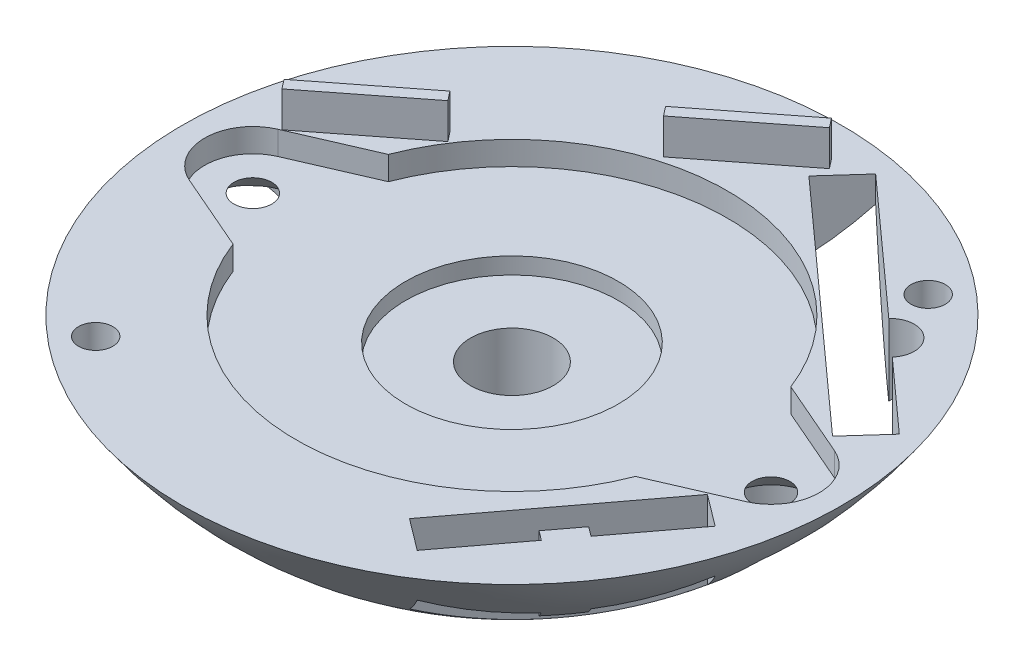
SolidWorks part; units mm, degrees
other "Markup1"
sketch "Sketch19" plane through (27.886, -16.1, -27.886) normal (0.7153, 0.5102, -0.4776) x (-0.4514, -0.1845, -0.8731)
ref_plane "Front Plane" through (0, 0, 0) normal (0, 0, 1) x (1, 0, 0)
ref_plane "Top Plane" through (0, 0, 0) normal (0, 1, 0) x (1, 0, 0)
ref_plane "Right Plane" through (0, 0, 0) normal (1, 0, 0) x (0, 0, -1)
sketch "Sketch1" plane through (0, 0, 0) normal (0, 0, 1) x (1, 0, 0)
  line L0 (0, -33.8) -> (0, 0)
  line L1 (33.8, 0) -> (0, 0)
  arc A0 (0, -33.8) -> (33.8, 0) centre (0, 0) ccw
  dimension "D1" = 33.8
revolve "Revolve1" add sketch "Sketch1" angle 360 about L0
sketch "Sketch2" plane through (0, 0, 0) normal (0, 1, 0) x (1, 0, 0)
  circle A0 centre (0, 0) radius 33.8 construction
  circle A1 centre (0, 0) radius 33.8
extrude "Cut-Extrude1" cut sketch "Sketch2" against normal blind 19.1
sketch "Sketch5" plane through (0, 0, 0) normal (0, 1, 0) x (1, 0, 0)
  line L0 (-21.92, 0) -> (21.92, 0) construction
  line L1 (-23.5443, 3.7427) -> (-17.0257, 6.5717)
  line L2 (-23.5443, -3.7427) -> (-17.0257, -6.5717)
  line L3 (17.0257, 6.5717) -> (23.5443, 3.7427)
  line L4 (23.5443, -3.7427) -> (17.0257, -6.5717)
  circle A0 centre (0, 0) radius 18.25
  arc A2 (-23.5443, 3.7427) -> (-23.5443, -3.7427) centre (-21.92, 0) ccw
  arc A3 (23.5443, 3.7427) -> (23.5443, -3.7427) centre (21.92, 0) cw
  point P12 (26, 0)
  point P15 (-26, 0)
  dimension "D1" = 36.5
  dimension "D2" = 43.84
  dimension "D3" = 52
  dimension "D4" = 23.46
extrude "Cut-Extrude2" cut sketch "Sketch5" against normal blind 2 from surface contours A3 L3 A0 L4 | L0 A0 | A0 L0 | L1 A2 L2 A0 region at (0, 0, -7.7455) region at (-18.0978, 0, 3.3715) region at (0, 0, 7.7455) region at (18.0978, 0, -3.3715) starting at face at (0, -19.1, 27.886)
sketch "Sketch6" plane through (0, -21.1, 0) normal (0, 1, 0) x (1, 0, 0)
  circle A0 centre (-21.92, 0) radius 1.6
  circle A1 centre (21.92, 0) radius 1.6
  dimension "D1" = 3.2
extrude "Cut-Extrude3" cut sketch "Sketch6" against normal up to next
sketch "Sketch7" plane through (0, -21.1, 0) normal (0, 1, 0) x (1, 0, 0)
  circle A0 centre (-21.92, 0) radius 4.08
  circle A1 centre (21.92, 0) radius 4.08
  arc A2 (-23.5443, 3.7427) -> (-23.5443, -3.7427) centre (-21.92, 0) ccw construction
  arc A3 (23.5443, -3.7427) -> (23.5443, 3.7427) centre (21.92, 0) ccw construction
extrude "Cut-Extrude4" cut sketch "Sketch7" against normal up to next from offset 2 offset against normal yes
sketch "Sketch8" plane through (0, -21.1, 0) normal (0, 1, 0) x (1, 0, 0)
  circle A0 centre (0, 0) radius 9
  dimension "D1" = 18
extrude "Cut-Extrude5" cut sketch "Sketch8" against normal blind 1.4
sketch "Sketch9" plane through (0, -22.5, 0) normal (0, 1, 0) x (1, 0, 0)
  circle A0 centre (0, 0) radius 3.5
  dimension "D1" = 7
extrude "Cut-Extrude6" cut sketch "Sketch9" against normal up to next
sketch "Sketch11" plane through (0, -19.1, 0) normal (0, 1, 0) x (1, 0, 0)
  line L0 (0, 0) -> (12.3789, 13.7482) construction
  line L1 (25.0879, 7.6875) -> (5.023, 25.754)
  line L2 (25.0879, 7.6875) -> (22.4114, 4.7149)
  line L3 (22.4114, 4.7149) -> (2.3465, 22.7814)
  line L4 (5.023, 25.754) -> (2.3465, 22.7814)
  line L5 (-9.6351, 0) -> (9.6351, 0) construction
  arc A1 (-17.0257, -6.5717) -> (17.0257, -6.5717) centre (0, 0) ccw construction
  circle A4 centre (17.6564, 14.3788) radius 2
  dimension "D4" = 48
  dimension "D5" = 4
  dimension "D1" = 27
  dimension "D2" = 4
  dimension "D3" = 18.5
  dimension "D6" = 10
extrude "Cut-Extrude8" cut sketch "Sketch11" against normal up to next contours L1 A4 | A4 L1 L4 L3 L2 | L1 A4 region at (13.5089, -19.1, -15.3263) region at (17.0885, -19.1, -13.748) region at (18.2244, -19.1, -15.0096)
sketch "Sketch12" plane through (0, -19.1, 0) normal (0, 1, 0) x (1, 0, 0)
  line L0 (-27.5388, 4.3869) -> (2.4056, 27.7821) construction
  line L1 (-27.5388, 4.3869) -> (-26.3075, 2.8109) construction
  line L2 (2.4056, 27.7821) -> (3.6369, 26.206) construction
  line L3 (-26.3075, 2.8109) -> (3.6369, 26.206) construction
  line L5 (2.3465, 22.7814) -> (22.4114, 4.7149) construction
  line L6 (-10.5, -19) -> (10.5, -19) construction
  line L7 (-10.5, -19) -> (-10.5, -21) construction
  line L8 (10.5, -19) -> (10.5, -21) construction
  line L9 (-10.5, -21) -> (10.5, -21) construction
  line L10 (13.2105, -21.224) -> (24.0431, -6.8486) construction
  line L11 (13.2105, -21.224) -> (10.5564, -19.224) construction
  line L12 (24.0431, -6.8486) -> (21.389, -4.8486) construction
  line L13 (10.5564, -19.224) -> (21.389, -4.8486) construction
  line L14 (15.9727, -12.0363) -> (0, 0) construction
  line L16 (0, 0) -> (0, -19) construction
  circle A0 centre (0, 0) radius 27.886 construction
  dimension "D1" = 38
  dimension "D2" = 2
  dimension "D3" = 100
  dimension "D4" = 18
  dimension "D5" = 2
  dimension "D6" = 21
  dimension "D7" = 2
  dimension "D8" = 19
  dimension "D9" = 20
  dimension "D10" = 53
sketch "Sketch13" plane through (0, -19.1, 0) normal (0, 1, 0) x (1, 0, 0)
  line L0 (13.2105, -21.224) -> (10.5564, -19.224) construction
  line L1 (13.2105, -21.224) -> (24.0431, -6.8486) construction
  line L2 (24.0431, -6.8486) -> (21.389, -4.8486) construction
  line L3 (10.5564, -19.224) -> (21.389, -4.8486) construction
  line L4 (13.2105, -21.224) -> (10.5564, -19.224)
  line L5 (13.2105, -21.224) -> (24.0431, -6.8486)
  line L6 (24.0431, -6.8486) -> (21.389, -4.8486)
  line L7 (10.5564, -19.224) -> (21.389, -4.8486)
  line L8 (16.9254, -14.6324) -> (18.7309, -12.2365)
  line L9 (16.9254, -14.6324) -> (17.7241, -15.2343)
  line L10 (18.7309, -12.2365) -> (19.5295, -12.8383)
  line L11 (17.7241, -15.2343) -> (19.5295, -12.8383)
  point P2 (18.6268, -14.0363)
  point P7 (18.6268, -14.0363)
  dimension "D1" = 1
  dimension "D2" = 3
extrude "Cut-Extrude9" cut sketch "Sketch13" against normal up to next contours L8 L10 L5 L6 L7 L4 L9 region at (17.2508, -19.1, 12.9994)
sketch "Sketch10" plane through (0, -19.1, 0) normal (0, 1, 0) x (1, 0, 0)
  line L0 (-16.0697, -19.1511) -> (16.0697, 19.1511) construction
  line L7 (0, -9.6351) -> (0, 9.6351) construction
  circle A0 centre (-16.0697, -19.1511) radius 1.45
  circle A3 centre (16.0697, 19.1511) radius 1.45
  circle A4 centre (0, 0) radius 25 construction
  point P0 (0, 0)
  point P2 (0, 0)
  dimension "D2" = 2.9
  dimension "D1" = 50
  dimension "D3" = 40
extrude "Cut-Extrude7" cut sketch "Sketch10" against normal up to next
sketch "Sketch14" plane through (0, -19.1, 0) normal (0, 1, 0) x (1, 0, 0)
  line L0 (-5.8192, 18.8181) -> (2.0609, 24.9747)
  line L1 (-5.8192, 18.8181) -> (-5.2035, 18.0301)
  line L2 (2.0609, 24.9747) -> (2.6766, 24.1867)
  line L3 (-5.2035, 18.0301) -> (2.6766, 24.1867)
  line L4 (-26.3075, 2.8109) -> (3.6369, 26.206) construction
  line L5 (-23.9434, 4.6579) -> (-16.0633, 10.8145)
  line L6 (-23.9434, 4.6579) -> (-23.3278, 3.8699)
  line L7 (-16.0633, 10.8145) -> (-15.4477, 10.0265)
  line L8 (-23.3278, 3.8699) -> (-15.4477, 10.0265)
  line L9 (2.4056, 27.7821) -> (3.6369, 26.206) construction
  line L10 (-27.5388, 4.3869) -> (-26.3075, 2.8109) construction
  dimension "D1" = 1
  dimension "D2" = 10
  dimension "D3" = 10
  dimension "D4" = 2
  dimension "D5" = 3
extrude "Boss-Extrude1" add sketch "Sketch14" along normal blind 3
sketch "Sketch18" plane through (0, -19.1, 0) normal (0, 1, 0) x (1, 0, 0)
  line L0 (-23.9434, 4.6579) -> (2.0609, 24.9747)
  line L1 (-23.9434, 4.6579) -> (-23.2829, 3.8125)
  line L2 (2.0609, 24.9747) -> (2.7214, 24.1293)
  line L3 (-23.2829, 3.8125) -> (2.7214, 24.1293)
extrude "Cut-Extrude12" [suppressed] cut sketch "Sketch18" along normal up to next
sketch "Sketch15" plane through (0, 0, 0) normal (0, 0, 1) x (1, 0, 0)
  line L0 (0, -19.1) -> (0, -33.6183) construction
  line L1 (-27.5388, -19.1) -> (2.4056, -19.1) construction
  line L2 (3.5, -33.6183) -> (-3.5, -33.6183) construction
  line L3 (3.5, -33.6183) -> (22.6018, -33.6183)
  line L4 (27.886, -19.1) -> (22.6018, -33.6183)
  arc A1 (0, -33.8) -> (33.8, 0) centre (0, 0) ccw construction
  arc A2 (3.5, -33.6183) -> (27.886, -19.1) centre (0, 0) ccw
  dimension "D1" = 70
revolve "Revolve2" [suppressed] add sketch "Sketch15" angle 360 about L0
sketch "Sketch16" plane through (0, -23.1, 0) normal (0, -1, 0) x (1, 0, 0)
  arc A2 (24.4678, 3.1867) -> (24.4678, -3.1867) centre (21.92, 0) ccw
  circle A4 centre (21.92, 0) radius 4.08
  arc A6 (-24.4678, -3.1867) -> (-24.4678, 3.1867) centre (-21.92, 0) ccw
  circle A8 centre (-21.92, 0) radius 4.08
  arc A10 (24.4678, -3.1867) -> (24.4678, 3.1867) centre (0, 0) ccw
  arc A11 (24.4678, -3.1867) -> (24.4678, 3.1867) centre (0, 0) ccw
  arc A12 (-24.4678, 3.1867) -> (-24.4678, -3.1867) centre (0, 0) ccw
  arc A13 (-24.4678, 3.1867) -> (-24.4678, -3.1867) centre (0, 0) ccw
  dimension "D1" = 0
  dimension "D2" = 0
extrude "Cut-Extrude10" [suppressed] cut sketch "Sketch16" along normal up to next
chamfer "Chamfer1" distance 2 angle 45 2 edges at (-21.92, -23.1, 1.6) (21.92, -23.1, 1.6)
